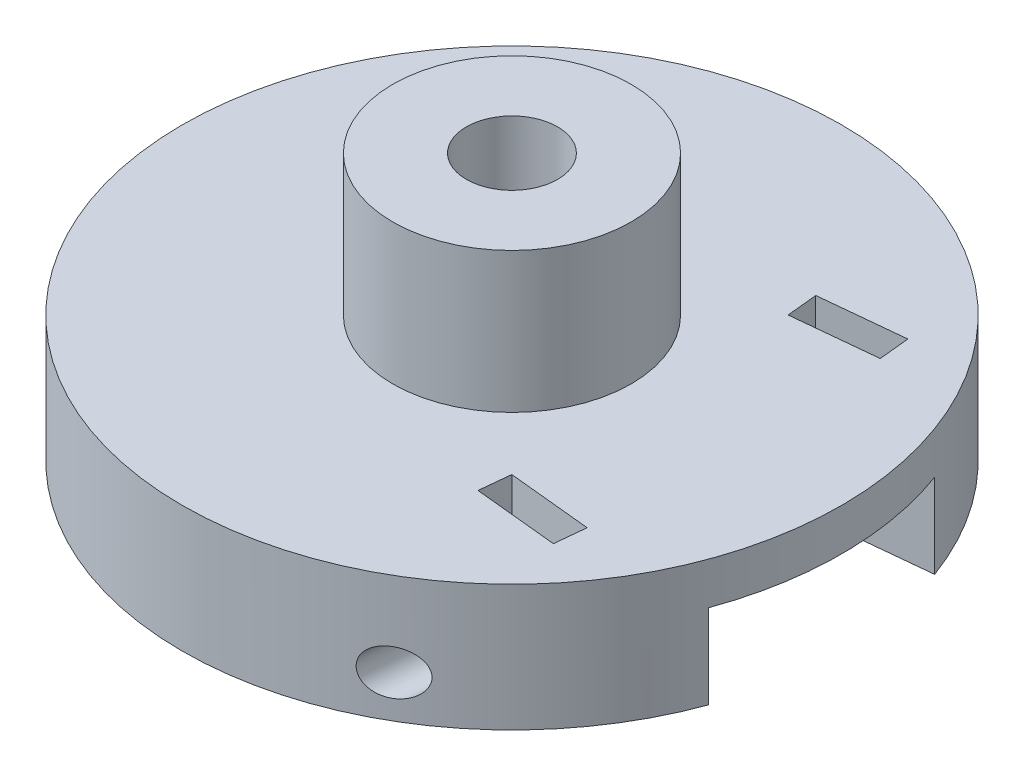
SolidWorks part; units mm, degrees
ref_plane "Спереди" through (0, 0, 0) normal (0, 0, 1) x (1, 0, 0)
ref_plane "Сверху" through (0, 0, 0) normal (0, 1, 0) x (1, 0, 0)
ref_plane "Справа" through (0, 0, 0) normal (1, 0, 0) x (0, 0, -1)
sketch "Эскиз1" plane through (0, 0, 0) normal (0, 1, 0) x (1, 0, 0)
  line L0 (-15.5, 2.19) -> (15.5, -5.29) construction
  line L1 (15.5, -5.29) -> (15.5, 5.29) construction
  line L2 (15.5, 5.29) -> (-15.5, -2.19) construction
  line L3 (-15.5, -2.19) -> (-15.5, 2.19) construction
  line L8 (-15.699, -4.1801) -> (22.1104, -7.961)
  line L10 (22.1104, 7.961) -> (-15.699, 4.1801)
  line L11 (-17.5, 2.19) -> (-17.5, -2.19)
  line L12 (-15.5, 2.19) -> (15.5, 5.29) construction
  line L13 (-15.5, -2.19) -> (15.5, -5.29) construction
  line L14 (-17.5, 0) -> (15.5, 0) construction
  line L15 (22.1005, 8.0605) -> (-15.709, 4.2796)
  line L16 (-17.6, 2.19) -> (-17.6, -2.19)
  line L17 (-15.709, -4.2796) -> (22.1005, -8.0605)
  circle A6 centre (0, 0) radius 23.5
  arc A9 (-15.699, 4.1801) -> (-17.5, 2.19) centre (-15.5, 2.19) ccw
  arc A10 (-17.5, -2.19) -> (-15.699, -4.1801) centre (-15.5, -2.19) ccw
  arc A11 (-15.709, 4.2796) -> (-17.6, 2.19) centre (-15.5, 2.19) ccw
  arc A12 (-17.6, -2.19) -> (-15.709, -4.2796) centre (-15.5, -2.19) ccw
  dimension "D3" = 47
  dimension "D4" = 0.1
extrude "Бобышка-Вытянуть1" add sketch "Эскиз1" along normal blind 3 contours A6
extrude "Вырез-Вытянуть1" cut sketch "Эскиз1<4>" along normal blind 3 contours L16 A12 L17 A6 L8 A10 L11 A9 L10 L15 A11 | L11 A10 L8 A6 L10 A9 region at (5.1051, 0, 0) region at (3.2015, 0, 6.1132)
sketch "Эскиз1<4>" plane through (0, 0, 0) normal (0, 1, 0) x (1, 0, 0) same geometry as "Эскиз1"
sketch "Эскиз2" plane through (0, 3, 0) normal (0, 1, 0) x (1, 0, 0)
  circle A1 centre (0, 0) radius 23.5
extrude "Бобышка-Вытянуть2" add sketch "Эскиз2" along normal blind 6
sketch "Эскиз3" plane through (0, 9, 0) normal (0, 1, 0) x (1, 0, 0)
  circle A0 centre (0, 0) radius 8.5
  dimension "D1" = 17
extrude "Бобышка-Вытянуть3" add sketch "Эскиз3" along normal blind 10
sketch "Эскиз4" plane through (0, 19, 0) normal (0, 1, 0) x (1, 0, 0)
  circle A0 centre (0, 0) radius 3.25
  dimension "D1" = 6.5
extrude "Вырез-Вытянуть2" cut sketch "Эскиз4" against normal blind 19
sketch "Эскиз5" plane through (0, 3, 0) normal (0, -1, 0) x (1, 0, 0)
  line L1 (5.7735, 0) -> (2.8868, 5)
  line L2 (2.8868, 5) -> (-2.8868, 5)
  line L3 (-2.8868, 5) -> (-5.7735, 0)
  line L4 (-5.7735, 0) -> (-2.8868, -5)
  line L5 (-2.8868, -5) -> (2.8868, -5)
  line L6 (2.8868, -5) -> (5.7735, 0)
  circle A0 centre (0, 0) radius 5 construction
  dimension "D1" = 10
extrude "Вырез-Вытянуть3" [suppressed] cut sketch "Эскиз5" against normal blind 4.5
sketch "Эскиз6" plane through (0, 3, 0) normal (0, -1, 0) x (1, 0, 0)
  line L3 (-15.709, -4.2796) -> (22.0753, -8.058)
  line L4 (22.0753, 8.058) -> (-15.709, 4.2796)
  line L5 (-17.6, 2.19) -> (-17.6, -2.19)
  line L6 (-15.709, -4.2796) -> (22.0753, -8.058)
  line L7 (22.0753, 8.058) -> (-15.709, 4.2796)
  line L8 (-17.6, 2.19) -> (-17.6, -2.19)
  arc A3 (22.0753, -8.058) -> (22.0753, 8.058) centre (0, 0) ccw
  arc A4 (-15.709, 4.2796) -> (-17.6, 2.19) centre (-15.5, 2.19) ccw
  arc A5 (-17.6, -2.19) -> (-15.709, -4.2796) centre (-15.5, -2.19) ccw
  arc A6 (22.0753, -8.058) -> (22.0753, 8.058) centre (0, 0) ccw
  arc A7 (-15.709, 4.2796) -> (-17.6, 2.19) centre (-15.5, 2.19) ccw
  arc A8 (-17.6, -2.19) -> (-15.709, -4.2796) centre (-15.5, -2.19) ccw
  dimension "D1" = 0
extrude "Вырез-Вытянуть4" cut sketch "Эскиз6" against normal blind 3
sketch "Эскиз7" plane through (0, 0, 0) normal (0, -1, 0) x (1, 0, 0)
  line L0 (9.8363, 9.8491) -> (15.8066, 10.4461)
  line L1 (15.8066, 10.4461) -> (15.5876, 12.6352)
  line L2 (15.5876, 12.6352) -> (9.6174, 12.0382)
  line L3 (9.6174, 12.0382) -> (9.8363, 9.8491)
  line L4 (-23.5, 0) -> (23.5, 0) construction
  line L5 (22.0753, 8.058) -> (-15.709, 4.2796) construction
  line L6 (-15.709, 4.2796) -> (22.0753, 8.058) construction
  line L7 (9.6174, -12.0382) -> (9.8363, -9.8491)
  line L8 (15.5876, -12.6352) -> (9.6174, -12.0382)
  line L9 (15.8066, -10.4461) -> (15.5876, -12.6352)
  line L10 (9.8363, -9.8491) -> (15.8066, -10.4461)
  arc A0 (22.0753, 8.058) -> (22.0753, -8.058) centre (0, 0) ccw construction
  arc A1 (22.0753, -8.058) -> (22.0753, 8.058) centre (0, 0) ccw construction
  point P14 (11.9751, 8.8007)
  dimension "D1" = 6
  dimension "D2" = 2.2
  dimension "D3" = 3
  dimension "D4" = 6
extrude "Вырез-Вытянуть5" cut sketch "Эскиз7" against normal through all
sketch "Эскиз8" plane through (-0.5793, 0, -5.7926) normal (0.0995, 0, 0.995) x (0.995, 0, -0.0995)
  line L0 (16.7675, 0) -> (10.7675, 0) construction
  line L1 (16.7675, 0) -> (10.7675, 0) construction
  line L2 (13.7675, 0) -> (13.7675, 6) construction
  line L3 (-15.2052, 6) -> (22.7675, 6) construction
  circle A0 centre (13.7675, 3) radius 1.6
  dimension "D1" = 3.2
extrude "Вырез-Вытянуть6" cut sketch "Эскиз8" against normal through all
mirror "Зеркальное отражение1" about plane through (0, 0, 0) normal (0, 0, 1) of "Вырез-Вытянуть6"
